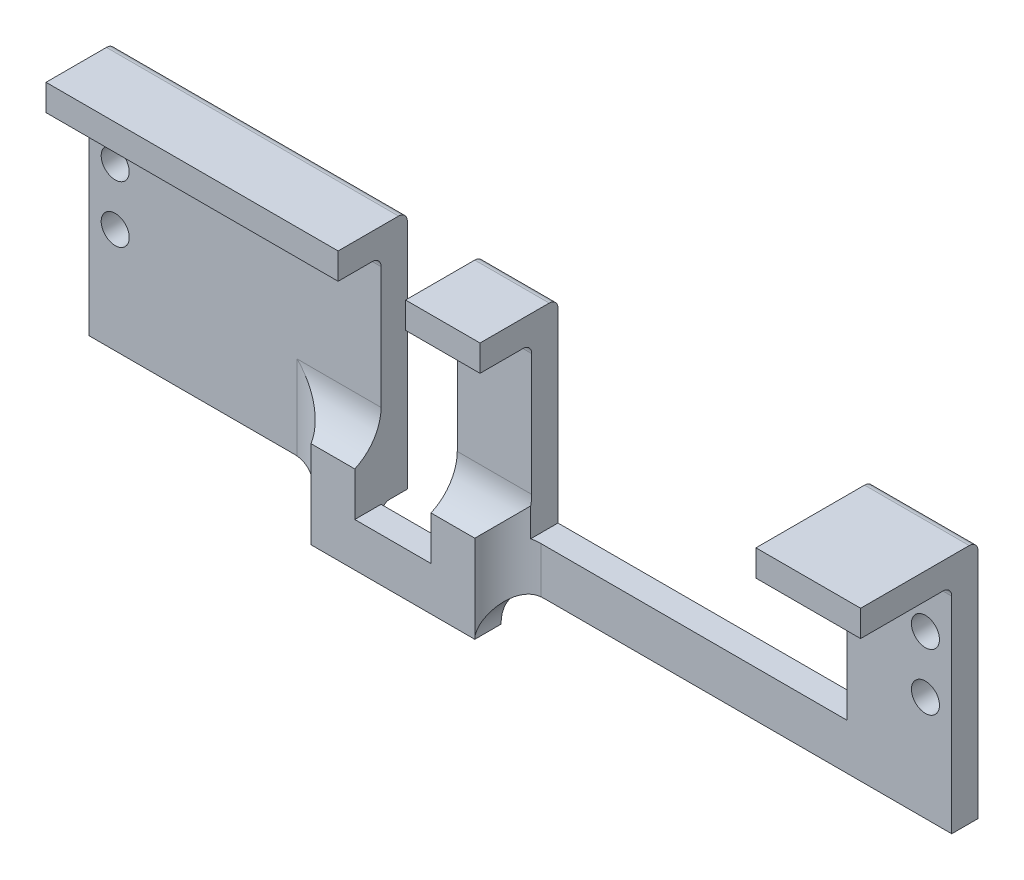
SolidWorks part; units mm, degrees
material "ABS"
ref_plane "前视基准面" through (0, 0, 0) normal (0, 0, 1) x (1, 0, 0)
ref_plane "上视基准面" through (0, 0, 0) normal (0, 1, 0) x (1, 0, 0)
ref_plane "右视基准面" through (0, 0, 0) normal (1, 0, 0) x (0, 0, -1)
other "Configuration Table"
sketch "草图1" plane through (0, 0, 0) normal (0, 0, 1) x (1, 0, 0)
  line L0 (-38.6665, 0) -> (31.2744, 0) construction
  line L1 (0, 22.4607) -> (0, -30.1372) construction
  line L2 (-49.25, 0) -> (49.25, 0)
  line L3 (-49.25, 0) -> (-49.25, 18.5)
  line L4 (-49.25, 18.5) -> (49.25, 18.5)
  line L5 (49.25, 0) -> (49.25, 18.5)
  circle A0 centre (-46.25, 3) radius 1.6
  circle A1 centre (-46.25, 9.5) radius 1.6
  circle A2 centre (46.25, 3) radius 1.6
  circle A3 centre (46.25, 9.5) radius 1.6
  dimension "D5" = 6.5
  dimension "D6" = 3.2
  dimension "D1" = 3
  dimension "D2" = 18.5
  dimension "D3" = 98.5
  dimension "D4" = 3
extrude "凸台-拉伸1" add sketch "草图1" along normal blind 3
sketch "草图2" plane through (0, 18.5, 0) normal (0, 1, 0) x (1, 0, 0)
  line L0 (49.25, -3) -> (49.25, 0) construction
  line L1 (-49.25, -3) -> (49.25, -3)
  line L2 (-49.25, -3) -> (-49.25, -24.5)
  line L3 (-49.25, -24.5) -> (49.25, -24.5)
  line L4 (49.25, -3) -> (49.25, -24.5)
  dimension "D1" = 21.5
extrude "凸台-拉伸2" add sketch "草图2" against normal blind 3
fillet "圆角1" radius 1 2 edges at (0, 15.5, 3) (0, 18.5, 0)
sketch "草图3" plane through (0, 0, 0) normal (0, -1, 0) x (1, 0, 0)
  line L4 (-49.25, 0) -> (49.25, 0)
  line L5 (49.25, 0) -> (49.25, 3)
  line L6 (49.25, 3) -> (-49.25, 3)
  line L7 (-49.25, 3) -> (-49.25, 0)
  line L8 (-49.25, 0) -> (49.25, 0)
  line L9 (49.25, 0) -> (49.25, 3)
  line L10 (49.25, 3) -> (-49.25, 3)
  line L11 (-49.25, 3) -> (-49.25, 0)
  dimension "D1" = 0
extrude "凸台-拉伸3" add sketch "草图3" along normal blind 9
sketch "草图4" plane through (0, 0, 0) normal (0, 0, -1) x (-1, 0, 0)
  line L0 (-49.25, 18.5) -> (49.25, 18.5) construction
  line L1 (7.2, 18.5) -> (15.9, 18.5)
  line L2 (7.2, 18.5) -> (7.2, -9)
  line L3 (7.2, -9) -> (15.9, -9)
  line L4 (15.9, 18.5) -> (15.9, -9)
  line L5 (49.25, -9) -> (-49.25, -9) construction
  line L6 (8.2, 14.25) -> (8.2, -7.75) construction
  line L7 (14.9, -7.75) -> (14.9, 14.25) construction
  dimension "D1" = 1
  dimension "D2" = 1
extrude "切除-拉伸1" cut sketch "草图4" against normal through all
sketch "草图5" plane through (0, 0, 0) normal (0, 0, -1) x (-1, 0, 0)
  line L0 (-49.25, 18.5) -> (7.2, 18.5) construction
  line L1 (-37.3, 18.5) -> (-1.3, 18.5)
  line L2 (-37.3, 18.5) -> (-37.3, -3.75)
  line L3 (-37.3, -3.75) -> (-1.3, -3.75)
  line L4 (-1.3, 18.5) -> (-1.3, -3.75)
  line L5 (-36.3, -2.75) -> (-2.3, -2.75) construction
  line L6 (-36.3, 14.25) -> (-36.3, -2.75) construction
  line L7 (-2.3, -2.75) -> (-2.3, 14.25) construction
  dimension "D1" = 1
  dimension "D2" = 1
  dimension "D3" = 1
extrude "切除-拉伸2" cut sketch "草图5" against normal through all
sketch "草图6" plane through (0, 18.5, 0) normal (0, 1, 0) x (1, 0, 0)
  line L0 (-7.2, -24.5) -> (-7.2, -1) construction
  line L1 (1.3, -24.5) -> (-7.2, -24.5)
  line L2 (1.3, -24.5) -> (1.3, -8.9)
  line L3 (1.3, -8.9) -> (-7.2, -8.9)
  line L4 (-7.2, -24.5) -> (-7.2, -8.9)
  line L6 (-8.2, -9.9) -> (2.3, -9.9) construction
  point P9 (-7.2, -7.8983)
  dimension "D1" = 1
extrude "切除-拉伸3" cut sketch "草图6" against normal through all
sketch "草图7" plane through (0, 18.5, 0) normal (0, 1, 0) x (1, 0, 0)
  line L0 (-49.25, -24.5) -> (-49.25, -1) construction
  line L1 (-15.9, -24.5) -> (-49.25, -24.5)
  line L2 (-15.9, -24.5) -> (-15.9, -7.9)
  line L3 (-15.9, -7.9) -> (-49.25, -7.9)
  line L4 (-49.25, -24.5) -> (-49.25, -7.9)
  line L5 (-15.9, -24.5) -> (-15.9, -1) construction
  line L6 (-35.2, -8.9) -> (-14.9, -8.9) construction
  point P7 (-15.9, -7.5195)
  dimension "D1" = 1
extrude "切除-拉伸4" cut sketch "草图7" against normal through all
sketch "草图8" plane through (0, 18.5, 0) normal (0, 1, 0) x (1, 0, 0)
  line L1 (37.3, -24.5) -> (37.3, -1) construction
  line L2 (49.25, -24.5) -> (37.3, -24.5)
  line L3 (49.25, -24.5) -> (49.25, -13.4)
  line L4 (49.25, -13.4) -> (37.3, -13.4)
  line L5 (37.3, -24.5) -> (37.3, -13.4)
  line L6 (36.3, -13.4) -> (40.3, -13.4) construction
extrude "切除-拉伸5" cut sketch "草图8" against normal through all
sketch "草图9" plane through (0, 0, 3) normal (0, 0, 1) x (1, 0, 0)
  line L0 (-7.2, 14.5) -> (-7.2, -9) construction
  line L1 (-2.2, -4) -> (-7.2, -4)
  line L2 (-2.2, -4) -> (-2.2, -14)
  line L3 (-2.2, -14) -> (-7.2, -14)
  line L4 (-7.2, -4) -> (-7.2, -14)
  line L5 (49.25, -9) -> (-7.2, -9) construction
  line L6 (-15.9, -9) -> (-15.9, 14.5) construction
  line L7 (-15.9, -4) -> (-20.9, -4)
  line L8 (-15.9, -4) -> (-15.9, -14)
  line L9 (-15.9, -14) -> (-20.9, -14)
  line L10 (-20.9, -4) -> (-20.9, -14)
  point P14 (0, 0)
  point P15 (-7.2, -5.2743)
  dimension "D1" = 5
  dimension "D2" = 5
  dimension "D3" = 5
extrude "凸台-拉伸5" add sketch "草图9" along normal blind 3
sketch "草图11" plane through (0, 0, 6) normal (0, 0, 1) x (1, 0, 0)
  line L0 (-7.2, -4) -> (-7.2, -14) construction
  line L1 (-7.2, -14) -> (-15.9, -14)
  line L2 (-7.2, -14) -> (-7.2, -9)
  line L3 (-7.2, -9) -> (-15.9, -9)
  line L4 (-15.9, -14) -> (-15.9, -9)
  line L5 (-15.9, -14) -> (-15.9, -4) construction
  point P8 (-7.2, -14)
  point P10 (-15.9, -9)
extrude "凸台-拉伸6" add sketch "草图11" against normal up to surface (3 mm away) up to face at (-18.4, -11.5, 3)
fillet "圆角2" radius 5 4 edges at (-20.9, -6.5, 3) (-2.2, -6.5, 3) (-4.7, -4, 3) (-18.4, -4, 3)
fillet "圆角3" radius 5 2 edges at (-20.9, -9, 4.5) (-2.2, -9, 4.5)
fillet "圆角4" radius 1 3 edges at (0.0913, -9, 3) (-20.6913, -9, 3) (-4.7, -9, 3)
